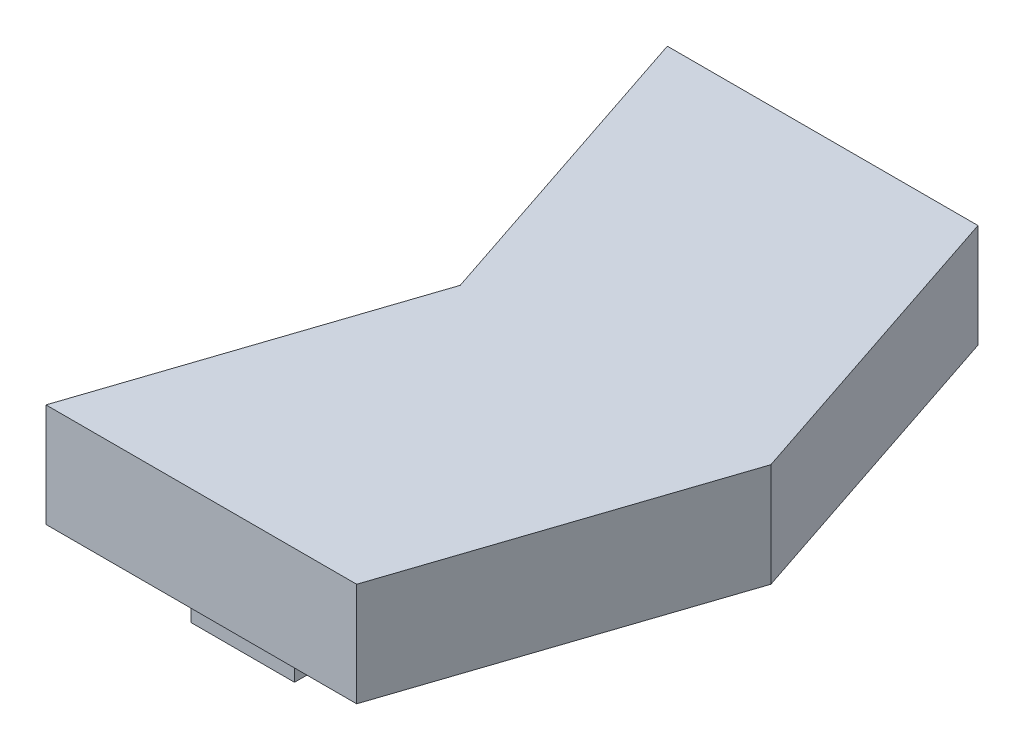
SolidWorks part; units mm, degrees
ref_plane "Front Plane" through (0, 0, 0) normal (0, 0, 1) x (1, 0, 0)
ref_plane "Top Plane" through (0, 0, 0) normal (0, 1, 0) x (1, 0, 0)
ref_plane "Right Plane" through (0, 0, 0) normal (1, 0, 0) x (0, 0, -1)
sketch "Sketch1" plane through (0, 0, 0) normal (0, 1, 0) x (1, 0, 0)
  line L0 (0, 0) -> (19.05, 0)
  line L1 (19.05, 0) -> (25.4, 19.05)
  line L2 (25.4, 19.05) -> (19.05, 38.1)
  line L3 (19.05, 38.1) -> (0, 38.1)
  line L4 (0, 38.1) -> (6.35, 19.05)
  line L5 (6.35, 19.05) -> (0, 0)
  dimension "D1" = 19.05
  dimension "D2" = 38.1
  dimension "D3" = 6.35
  dimension "D5" = 19.05
extrude "Boss-Extrude1" add sketch "Sketch1" along normal blind 6.35
sketch "Sketch2" plane through (0, 0, 0) normal (0, -1, 0) x (1, 0, 0)
  line L0 (25.4, -19.05) -> (6.35, -19.05) construction
  line L1 (6.35, -19.05) -> (0, 0) construction
  circle A0 centre (15.24, -19.05) radius 5.635
  dimension "D1" = 11.27
  dimension "D2" = 8.89
extrude "Cut-Extrude1" cut sketch "Sketch2" against normal blind 3.208 contours A0
sketch "Sketch3" plane through (0, 0, 0) normal (0, -1, 0) x (1, 0, 0)
  line L8 (16.51, -24.54) -> (13.97, -24.54)
  line L9 (16.51, -24.54) -> (16.51, -28.35)
  line L10 (13.97, -24.54) -> (13.97, -28.35)
  line L11 (16.51, -28.35) -> (13.97, -28.35)
  circle A3 centre (15.24, -19.05) radius 5.635 construction
  dimension "D1" = 2.54
  dimension "D2" = 3.81
extrude "Haptic Wire Cutout" cut sketch "Sketch3" against normal blind 3.208
ref_plane "MidPlane" through (0, 0, -19.05) normal (0, 0, -1) x (-1, 0, 0)
sketch "Sketch4" plane through (0, 0, 0) normal (0, -1, 0) x (1, 0, 0)
  line L0 (19.05, -38.1) -> (0, -38.1) construction
  line L1 (13.97, -36.83) -> (7.62, -36.83)
  line L2 (13.97, -36.83) -> (13.97, -34.29)
  line L3 (13.97, -34.29) -> (7.62, -34.29)
  line L4 (7.62, -36.83) -> (7.62, -34.29)
  line L5 (0, -4.8895) -> (0, 4.8895) construction
  dimension "D1" = 2.54
  dimension "D2" = 6.35
  dimension "D3" = 1.27
  dimension "D4" = 7.62
extrude "Pins" add sketch "Sketch4" along normal blind 2.032
mirror "Mirror1" about plane through (0, 0, -19.05) normal (0, 0, -1) of "Pins"
ref_point "Point1"
ref_axis "Axis1" through (0, 6.35, -38.1) along (0, 0, 1)
sketch "Sketch5" plane through (0, 6.35, 0) normal (0, 1, 0) x (1, 0, 0)
  line L0 (0, 38.1) -> (0, 0) construction
  line L1 (0, 19.05) -> (25.4, 19.05) construction
equation "\"Arrow Height\"= 1.5in"
equation "\"Button Height\"= 2in"
equation "\"Button Width\"= 4in"
equation "\"Haptic Diameter\"= 10mm"
equation "\"Haptic Thickness\"= 2.7mm"
equation "\"D2@Sketch1\"=\"Arrow Height\""
equation "\"D5@Sketch1\"=\"Arrow Height\"/2"
equation "\"D1@Sketch2\"=\"Haptic Diameter\"+.05in"
equation "\"D1@Cut-Extrude1\"=\"Haptic Thickness\" +.02"
equation "\"D1@Haptic Wire Cutout\"=\"Haptic Thickness\"+.02"
equation "\"Arrow Spacing\"= 1in"
equation "\"Arrow Width\"= 01in"
equation "\"Haptic Wire Angle\"= 63.43"
equation "\"Haptic Wire Width\"= .1in"
equation "\"Haptic Wire Height\"= .15in"
